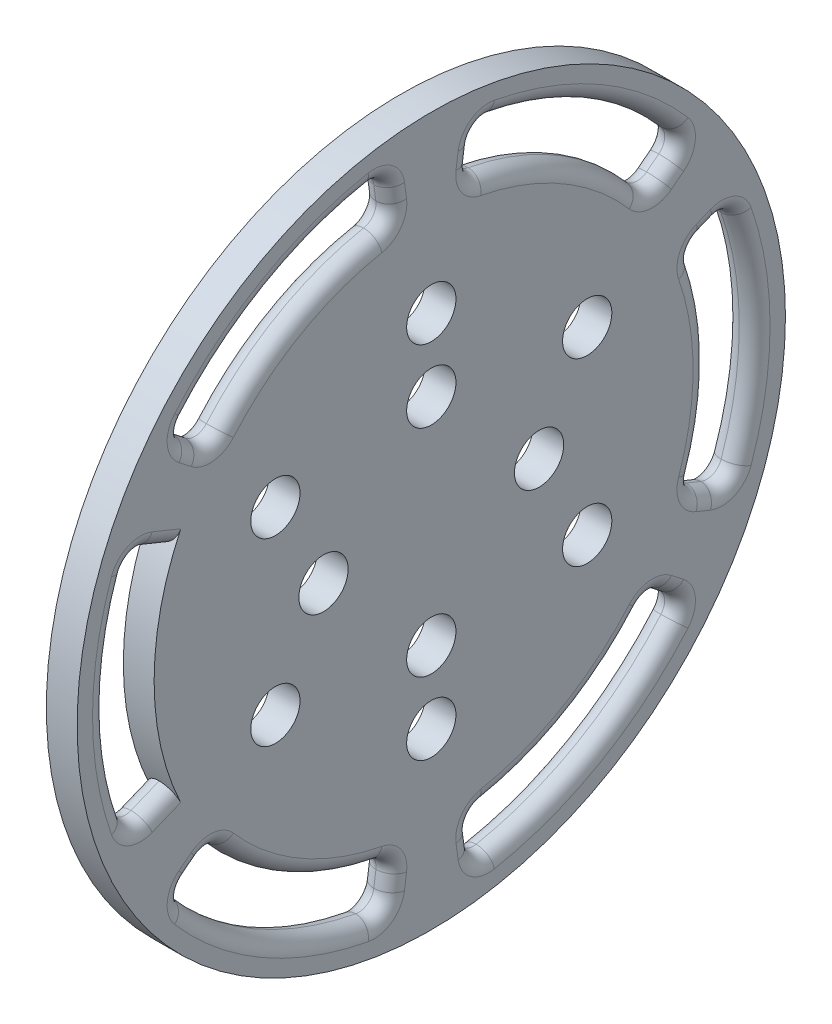
SolidWorks part; units mm, degrees
ref_plane "Front Plane" through (0, 0, 0) normal (0, 0, 1) x (1, 0, 0)
ref_plane "Top Plane" through (0, 0, 0) normal (0, 1, 0) x (1, 0, 0)
ref_plane "Right Plane" through (0, 0, 0) normal (1, 0, 0) x (0, 0, -1)
sketch "Sketch1" plane through (0, 0, 0) normal (1, 0, 0) x (0, 0, -1)
  line L0 (-2.8739, 20.8024) -> (-2.4634, 17.8306)
  line L1 (0, 11.6913) -> (-10.125, -5.8457) construction
  line L2 (-10.125, -5.8457) -> (10.125, -5.8457) construction
  line L3 (10.125, -5.8457) -> (0, 11.6913) construction
  line L4 (2.4634, 17.8306) -> (2.8739, 20.8024)
  line L5 (16.6735, 6.782) -> (19.4524, 7.9123)
  line L6 (16.5785, 12.8901) -> (14.2101, 11.0487)
  line L7 (14.2101, -11.0487) -> (16.5785, -12.8901)
  line L8 (19.4524, -7.9123) -> (16.6735, -6.782)
  line L9 (-2.4634, -17.8306) -> (-2.8739, -20.8024)
  line L10 (2.8739, -20.8024) -> (2.4634, -17.8306)
  line L11 (-16.6735, -6.782) -> (-19.4524, -7.9123)
  line L12 (-16.5785, -12.8901) -> (-14.2101, -11.0487)
  line L13 (-14.2101, 11.0487) -> (-16.5785, 12.8901)
  line L14 (-19.4524, 7.9123) -> (-16.6735, 6.782)
  circle A0 centre (0, 0) radius 23
  circle A1 centre (0, 0) radius 16 construction
  circle A2 centre (0, 0) radius 5.8457 construction
  circle A3 centre (0, 11.6913) radius 1.6
  circle A4 centre (10.125, 5.8457) radius 1.6
  circle A5 centre (10.125, -5.8457) radius 1.6
  circle A6 centre (0, -11.6913) radius 1.6
  circle A7 centre (-10.125, -5.8457) radius 1.6
  circle A8 centre (-10.125, 5.8457) radius 1.6
  arc A9 (-2.8739, 20.8024) -> (-16.5785, 12.8901) centre (0, 0) ccw
  arc A10 (-2.4634, 17.8306) -> (-14.2101, 11.0487) centre (0, 0) ccw
  circle A11 centre (0, 0) radius 18 construction
  circle A12 centre (0, 0) radius 21 construction
  arc A13 (14.2101, 11.0487) -> (2.4634, 17.8306) centre (0, 0) ccw
  arc A14 (16.5785, 12.8901) -> (2.8739, 20.8024) centre (0, 0) ccw
  arc A15 (19.4524, -7.9123) -> (19.4524, 7.9123) centre (0, 0) ccw
  arc A16 (16.6735, -6.782) -> (16.6735, 6.782) centre (0, 0) ccw
  arc A17 (2.8739, -20.8024) -> (16.5785, -12.8901) centre (0, 0) ccw
  arc A18 (-16.5785, -12.8901) -> (-2.8739, -20.8024) centre (0, 0) ccw
  arc A19 (-14.2101, -11.0487) -> (-2.4634, -17.8306) centre (0, 0) ccw
  arc A20 (-16.6735, 6.782) -> (-16.6735, -6.782) centre (0, 0) ccw
  arc A21 (-19.4524, 7.9123) -> (-19.4524, -7.9123) centre (0, 0) ccw
  arc A22 (14.2101, -11.0487) -> (2.4634, -17.8306) centre (0, 0) cw
  point P21 (0, 0)
  point P50 (0, 0)
  dimension "D1" = 46
  dimension "D2" = 32
  dimension "D4" = 3.2
  dimension "D3" = 20.25
  dimension "D5" = 2
  dimension "D6" = 2
  dimension "D7" = 6
  dimension "D8" = 6
extrude "Boss-Extrude1" add sketch "Sketch1" along normal blind 2 contours A0 A22 L7 A17 L10 A21 L14 A20 L11 A14 L6 A13 L4 A8 A7 A6 A5 A4 A3 L0 A10 L13 A9 L8 A16 L5 A15 L12 A19 L9 A18
fillet "Fillet1" radius 1 46 edges at (2, 18.1865, 10.5) (0, 18.1865, 10.5) (2, 15.5885, 9) (0, 15.5885, 9) (2, 15.5885, -9) (0, 15.5885, -9) (2, 18.1865, -10.5) (0, 18.1865, -10.5) (2, 0, -18) (0, 0, -18) (2, 0, -21) (0, 0, -21) (2, -18.1865, -10.5) (0, -18.1865, -10.5) (2, -15.5885, -9) (0, -15.5885, -9) (2, -18.1865, 10.5) (0, -18.1865, 10.5) (2, -15.5885, 9) (0, -15.5885, 9) (2, -7.3472, 18.0629) (0, -7.3472, 18.0629) (2, 7.3472, 18.0629) (0, 7.3472, 18.0629) (2, 11.9694, 15.3943) (0, 11.9694, 15.3943) (2, 19.3165, 2.6686) (0, 19.3165, 2.6686) (2, 11.9694, -15.3943) (0, 11.9694, -15.3943) (2, 19.3165, -2.6686) (0, 19.3165, -2.6686) (2, -7.3472, -18.0629) (0, -7.3472, -18.0629) (2, 7.3472, -18.0629) (0, 7.3472, -18.0629) (2, -11.9694, -15.3943) (0, -11.9694, -15.3943) (2, -19.3165, -2.6686) (0, -19.3165, -2.6686) (2, -19.3165, 2.6686) (0, -19.3165, 2.6686) (2, -11.9694, 15.3943) (0, -11.9694, 15.3943) (2, 0, 21) (0, 0, 21)
sketch "Sketch2" plane through (2, 0, 0) normal (1, 0, 0) x (0, 0, -1)
  circle A0 centre (0, 0) radius 7 construction
  circle A1 centre (7, 0) radius 1.6
  circle A4 centre (10.125, -5.8457) radius 1.6 construction
  circle A5 centre (0, -7) radius 1.6
  circle A6 centre (-7, 0) radius 1.6
  circle A7 centre (0, 7) radius 1.6
  point P7 (-7.487, -1.4524)
  point P8 (0, 0)
  point P16 (0, 0)
  dimension "D1" = 14
  dimension "D2" = 4
extrude "Cut-Extrude1" cut sketch "Sketch2" against normal through all
